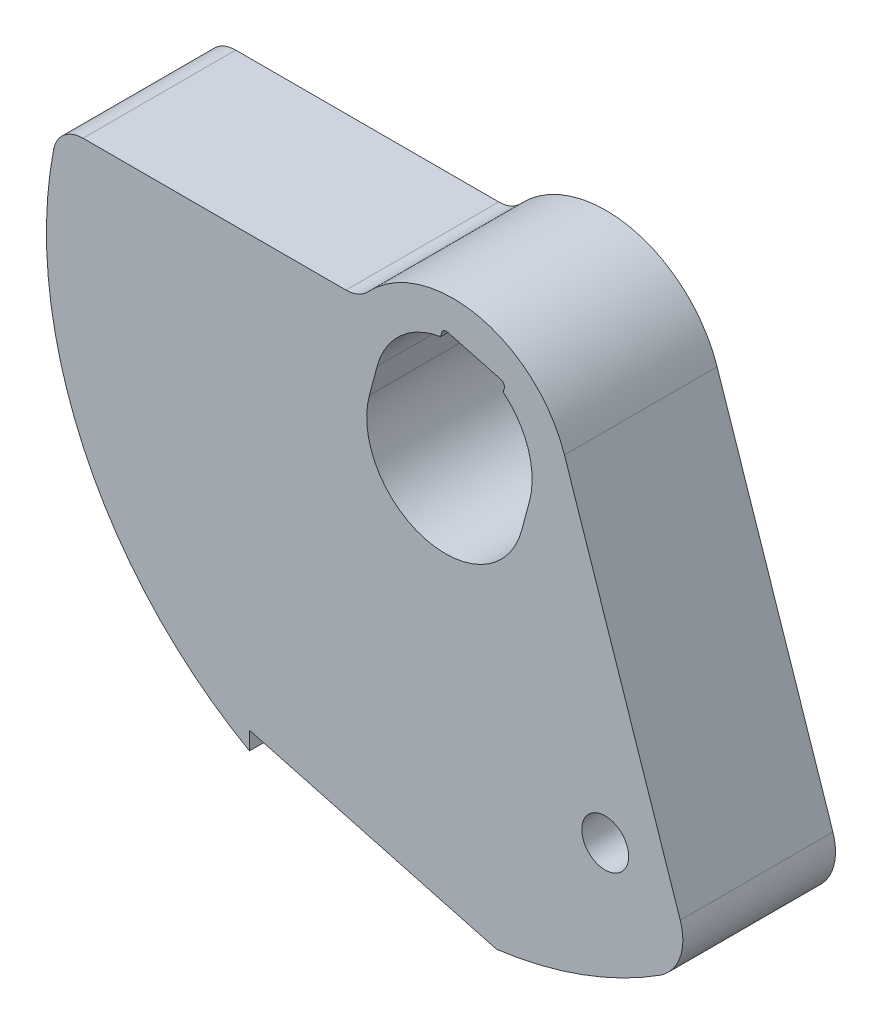
SolidWorks part; units mm, degrees
ref_plane "Front Plane" through (0, 0, 0) normal (0, 0, 1) x (1, 0, 0)
ref_plane "Top Plane" through (0, 0, 0) normal (0, 1, 0) x (1, 0, 0)
ref_plane "Right Plane" through (0, 0, 0) normal (1, 0, 0) x (0, 0, -1)
sketch "Sketch1" plane through (0, 0, 0) normal (0, 0, 1) x (1, 0, 0)
  line L0 (0, 40.7088) -> (0, -42.4788) construction
  line L1 (50.0011, 0) -> (-47.9361, 0) construction
  line L2 (0, 0) -> (4.815, 17.9697) construction
  line L3 (-7.4706, 2.0017) -> (6.4814, -1.7367) construction
  line L4 (-7.0762, 3.4738) -> (6.8758, -0.2646) construction
  line L5 (-3.8765, 1.0387) -> (-3.482, 2.5108)
  line L6 (4.2709, 0.4334) -> (3.8765, -1.0387)
  line L7 (-5.0653, 5.08) -> (-18.4566, 5.08)
  line L8 (6.0531, 3.3717) -> (7.0281, 0.4672)
  line L9 (12.9403, -3.6173) -> (17.147, -10.9034)
  line L10 (0, 0) -> (5.8427, -10.1199) construction
  line L11 (0, 0) -> (43.883, -11.7584) construction
  line L12 (8.128, 40.7088) -> (8.128, -42.4788) construction
  line L13 (50.0011, -12.7) -> (-47.9361, -12.7) construction
  line L14 (-1.0387, -3.8765) -> (-9.0244, -1.7367) construction
  line L15 (-9.9822, -16.7843) -> (-9.9822, -17.6991)
  line L16 (-9.9822, -16.7843) -> (2.5931, -20.1539)
  line L17 (2.8088, 5.0851) -> (0.11, 5.8082)
  line L18 (1.4594, 5.4467) -> (-6.5263, 7.5864) construction
  line L21 (2.9359, 4.578) -> (2.9884, 4.774)
  line L24 (-0.2536, 5.4326) -> (-0.2011, 5.6286)
  arc A0 (-3.8765, 1.0387) -> (3.8765, -1.0387) centre (0, 0) ccw
  arc A1 (6.1601, -0.0728) -> (6.1791, 0) centre (0.3944, 1.4721) ccw
  arc A2 (4.2709, 0.4334) -> (2.9359, 4.578) centre (0.3944, 1.4721) ccw
  arc A3 (7.0281, 0.4672) -> (12.6001, -3.4269) centre (12.446, 2.286) ccw
  arc A4 (6.0531, 3.3717) -> (-3.9548, 5.5602) centre (0.3944, 1.4721) ccw
  arc A5 (-19.953, 3.8443) -> (-9.9822, -17.6991) centre (0, 0) ccw
  arc A6 (12.6001, -3.4269) -> (12.9403, -3.6173) centre (12.6104, -3.8078) cw
  arc A7 (2.5931, -20.1539) -> (17.147, -10.9034) centre (0, 0) ccw
  arc A8 (-18.4566, 5.08) -> (-19.953, 3.8443) centre (-18.4566, 3.556) ccw
  arc A9 (-5.0653, 5.08) -> (-3.9548, 5.5602) centre (-5.0653, 6.604) ccw
  circle A10 centre (8.128, -12.7) radius 1.1938
  arc A11 (-0.2536, 5.4326) -> (-3.482, 2.5108) centre (0.3944, 1.4721) ccw
  arc A12 (2.8088, 5.0851) -> (2.9884, 4.774) centre (2.7431, 4.8397) cw
  arc A13 (-0.2011, 5.6286) -> (0.11, 5.8082) centre (0.0443, 5.5629) cw
  point P35 (-9.9822, 40.7088)
  point P36 (-9.9822, -42.4788)
  point P48 (1.5947, -0.4273)
  point P50 (6.4097, 17.5424)
  point P51 (-1.5947, 0.4273)
  point P52 (3.2202, 18.397)
  dimension "D1" = 8.0264
  dimension "D4" = 11.938
  dimension "D6" = 11.43
  dimension "D11" = 40.64
  dimension "D12" = 0.381
  dimension "D16" = 1.524
  dimension "D17" = 1.524
  dimension "D20" = 2.3876
  dimension "D24" = 0.254
  dimension "D2" = 15
  dimension "D5" = 5.08
  dimension "D7" = 2.286
  dimension "D8" = 12.446
  dimension "D9" = 60
  dimension "D10" = 9.398
  dimension "D13" = 15
  dimension "D14" = 18.796
  dimension "D15" = 9.9822
  dimension "D22" = 3.302
  dimension "D23" = 1.651
  dimension "D3" = 1.524
  dimension "D18" = 8.128
  dimension "D19" = 12.7
  dimension "D21" = 9.652
extrude "Boss-Extrude1" add sketch "Sketch1" against normal blind 7.7724 contours A9 L7 A8 A5 L15 L16 A7 L9 A6 A3 L8 A4 A10 A2 L6 A0 L5 region at (-3.022, -7.1767, 0)
sketch "Sketch2" plane through (0, 0, 0) normal (0, 0, 1) x (1, 0, 0)
  line L0 (7.0281, 0.4672) -> (12.5499, -15.9813)
  arc A0 (2.5931, -20.1539) -> (17.147, -10.9034) centre (0, 0) ccw construction
extrude "Cut-Extrude1" cut sketch "Sketch2" against normal through all and the other way through all
fillet "Fillet1" radius 2.54 1 edges at (12.5499, -15.9813, -3.8862)
